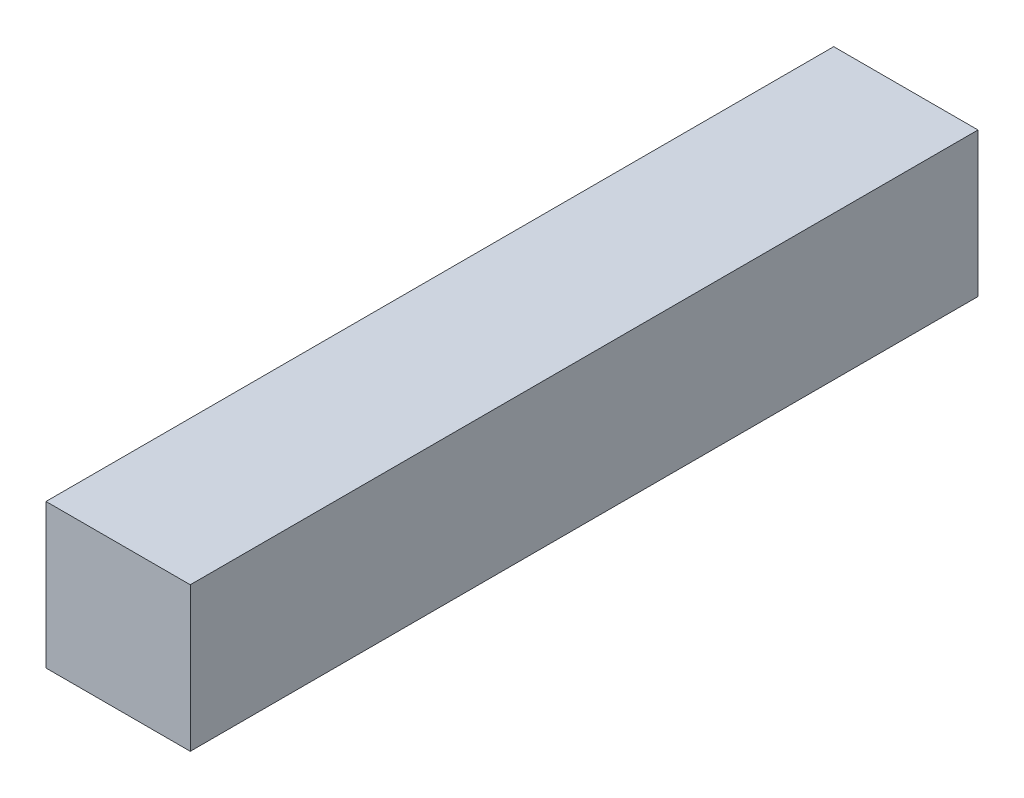
SolidWorks part; units mm, degrees
ref_plane "Front Plane" through (0, 0, 0) normal (0, 0, 1) x (1, 0, 0)
ref_plane "Top Plane" through (0, 0, 0) normal (0, 1, 0) x (1, 0, 0)
ref_plane "Right Plane" through (0, 0, 0) normal (1, 0, 0) x (0, 0, -1)
sketch "Sketch1" plane through (0, 0, 0) normal (0, 0, 1) x (1, 0, 0)
  line L1 (-12.7, -12.7) -> (12.7, -12.7)
  line L2 (-12.7, -12.7) -> (-12.7, 12.7)
  line L3 (-12.7, 12.7) -> (12.7, 12.7)
  line L4 (12.7, -12.7) -> (12.7, 12.7)
  line L5 (-12.7, -12.7) -> (12.7, 12.7) construction
  line L6 (-12.7, 12.7) -> (12.7, -12.7) construction
  point P0 (0, 0)
  dimension "D1" = 25.4
  dimension "D2" = 25.4
extrude "Boss-Extrude1" add sketch "Sketch1" along normal mid plane 138.683
